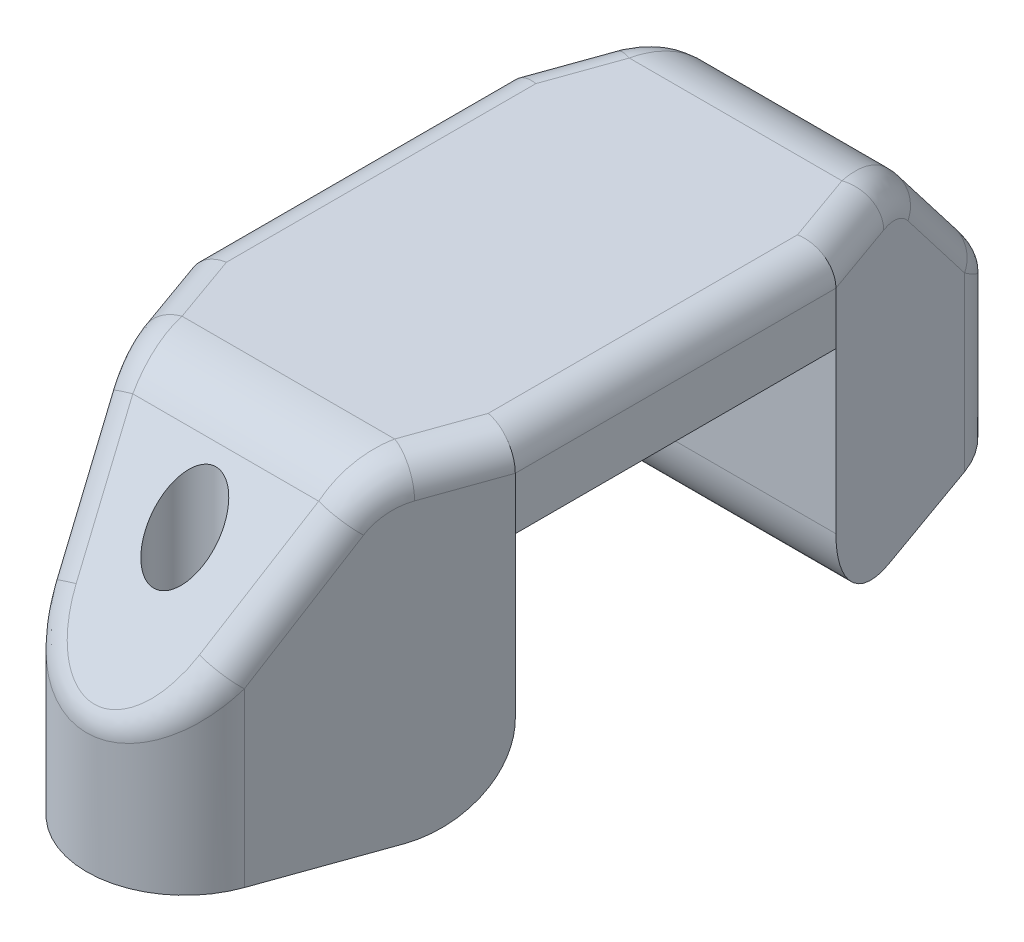
SolidWorks part; units mm, degrees
ref_plane "Front Plane" through (0, 0, 0) normal (0, 0, 1) x (1, 0, 0)
ref_plane "Top Plane" through (0, 0, 0) normal (0, 1, 0) x (1, 0, 0)
ref_plane "Right Plane" through (0, 0, 0) normal (1, 0, 0) x (0, 0, -1)
sketch "Sketch1" plane through (0, 0, 0) normal (0, 1, 0) x (1, 0, 0)
  line L0 (0, 0) -> (12.9383, 0) construction
  line L1 (-6.35, -6.223) -> (6.35, -6.223)
  line L2 (-6.35, -6.223) -> (-6.35, 6.223)
  line L3 (-6.35, 6.223) -> (6.35, 6.223)
  line L4 (6.35, -6.223) -> (6.35, 6.223)
  line L5 (-6.35, -6.223) -> (6.35, 6.223) construction
  line L6 (-6.35, 6.223) -> (6.35, -6.223) construction
  line L7 (-6.35, -6.223) -> (-3.5893, -13.9778)
  line L8 (6.35, -6.223) -> (3.5893, -13.9778)
  line L9 (-6.35, 6.223) -> (-3.5893, 13.9778)
  line L10 (6.35, 6.223) -> (3.5893, 13.9778)
  circle A0 centre (0, -12.7) radius 1.2065
  circle A1 centre (0, 12.7) radius 1.2065
  circle A2 centre (0, -12.7) radius 3.81
  circle A4 centre (0, 12.7) radius 3.81
  point P0 (0, 0)
  dimension "D3" = 2.413
  dimension "D4" = 25.4
  dimension "D5" = 7.62
  dimension "D1" = 12.446
  dimension "D2" = 12.7
extrude "Boss-Extrude1" add sketch "Sketch1" along normal blind 12.7 contours A4 A1 | L10 A4 L9 L3 | L1 L4 L3 L2 | A2 L8 L1 L7 | A2 A0 region at (0, 0, 0) region at (0, 0, 8.2905) region at (0, 0, -8.2905) region at (-0.63, 0, 9.0518) region at (0, 0, -16.4022)
sketch "Sketch2" plane through (6.35, 0, 0) normal (1, 0, 0) x (0, 0, -1)
  line L0 (6.223, 12.7) -> (6.223, 0) construction
  line L1 (-6.223, 9.398) -> (6.223, 9.398)
  line L2 (-6.223, 9.398) -> (-6.223, 0)
  line L3 (-6.223, 0) -> (6.223, 0)
  line L4 (6.223, 9.398) -> (6.223, 0)
  line L5 (-6.223, 9.398) -> (6.223, 0) construction
  line L6 (-6.223, 0) -> (6.223, 9.398) construction
  point P0 (0, 4.699)
  dimension "D1" = 9.398
extrude "Cut-Extrude1" cut sketch "Sketch2" against normal through all
sketch "Sketch3" plane through (6.35, 0, 0) normal (1, 0, 0) x (0, 0, -1)
  line L0 (-16.51, 5.1324) -> (-16.51, 12.7)
  line L1 (-16.51, 12.7) -> (-16.51, 0) construction
  line L2 (-16.51, 12.7) -> (-10.16, 12.7)
  line L3 (-6.223, 12.7) -> (-13.9778, 12.7) construction
  line L4 (-10.16, 12.7) -> (-16.51, 5.1324)
  line L5 (0, 0) -> (0, 16.4183) construction
  line L6 (10.16, 12.7) -> (16.51, 5.1324)
  line L7 (16.51, 12.7) -> (10.16, 12.7)
  line L8 (16.51, 5.1324) -> (16.51, 12.7)
  dimension "D1" = 50
  dimension "D2" = 6.35
extrude "Cut-Extrude2" cut sketch "Sketch3" against normal through all
fillet "Fillet1" radius 3.175 4 edges at (0, 0, -6.223) (0, 0, 6.223) (0, 12.7, -10.16) (0, 12.7, 10.16)
fillet "Fillet2" radius 1.27 16 edges at (-5.9128, 12.7, -7.4512) (5.9128, 12.7, -7.4512) (4.0995, 9.858, -12.5447) (0, 5.1324, -16.51) (-4.0995, 9.858, -12.5447) (5.9128, 12.7, 7.4512) (-5.9128, 12.7, 7.4512) (-4.9978, 12.4025, 10.0213) (-4.0995, 9.858, 12.5447) (0, 5.1324, 16.51) (4.0995, 9.858, 12.5447) (4.9978, 12.4025, -10.0213) (-4.9978, 12.4025, -10.0213) (-6.35, 12.7, 0) (6.35, 12.7, 0) (4.9978, 12.4025, 10.0213)
